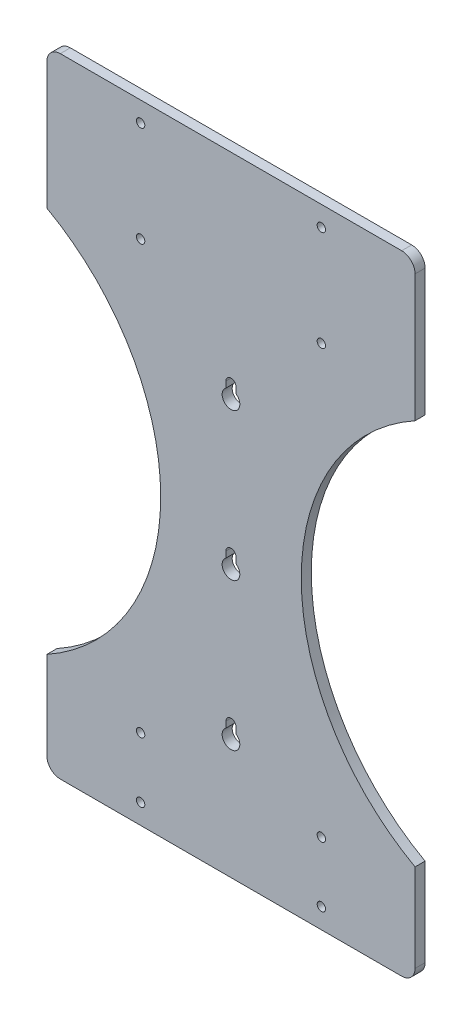
SolidWorks part; units mm, degrees
material "PC High Viscosity"
ref_plane "Front Plane" through (0, 0, 0) normal (0, 0, 1) x (1, 0, 0)
ref_plane "Top Plane" through (0, 0, 0) normal (0, 1, 0) x (1, 0, 0)
ref_plane "Right Plane" through (0, 0, 0) normal (1, 0, 0) x (0, 0, -1)
sketch "Sketch1" plane through (0, 0, 0) normal (0, 0, 1) x (1, 0, 0)
  line L0 (-174.625, 151.522) -> (-174.625, 311.15)
  line L1 (-174.625, -311.15) -> (174.625, -311.15)
  line L2 (-174.625, -311.15) -> (-174.625, -215.022)
  line L3 (-174.625, 311.15) -> (174.625, 311.15)
  line L4 (174.625, -311.15) -> (174.625, -215.022)
  line L5 (-174.625, -311.15) -> (174.625, 311.15) construction
  line L6 (-174.625, 311.15) -> (174.625, -311.15) construction
  line L7 (0, 311.15) -> (0, -311.15) construction
  line L8 (174.625, 151.522) -> (174.625, 311.15)
  arc A0 (-174.625, -215.022) -> (-174.625, 151.522) centre (-276.225, -31.75) ccw
  arc A1 (174.625, -215.022) -> (174.625, 151.522) centre (276.225, -31.75) cw
  point P0 (0, 0)
  dimension "D3" = 419.1
  dimension "D1" = 622.3
  dimension "D2" = 349.25
  dimension "D4" = 279.4
  dimension "D5" = 101.6
extrude "Boss-Extrude1" add sketch "Sketch1" along normal blind 9.525
sketch "Sketch2" plane through (0, 0, 9.525) normal (0, 0, 1) x (1, 0, 0)
  line L0 (0, 311.15) -> (0, -311.15) construction
  line L1 (174.625, 311.15) -> (-174.625, 311.15) construction
  line L2 (-174.625, -311.15) -> (174.625, -311.15) construction
  line L3 (-66.675, -31.75) -> (66.675, -31.75) construction
  arc A0 (-174.625, -215.022) -> (-174.625, 151.522) centre (-276.225, -31.75) ccw construction
  arc A1 (174.625, 151.522) -> (174.625, -215.022) centre (276.225, -31.75) ccw construction
  point P6 (0, -191.262)
  point P7 (0, 88.138)
  point P16 (0, -51.562)
  dimension "D2" = 119.888
  dimension "D1" = 279.4
  dimension "D3" = 139.7
hole_wizard "V (0.377) Diameter Slot1" positions "Sketch3" profile "Sketch5" size "V" standard "ANSI Inch" slot yes end condition through all
sketch "Sketch3" plane through (0, 0, 9.525) normal (0, 0, 1) x (1, 0, 0)
  line L0 (0, -202.3745) -> (0, -180.1495) construction
  point P0 (0, -191.262)
  point P3 (0, 88.138)
  point P8 (0, -51.562)
  dimension "D1" = 22.225
sketch "Sketch5" plane through (0, -191.262, 9.525) normal (1, 0, 0) x (0, -1, 0)
  line L0 (0, 0) -> (0, 9.525)
  line L1 (0, 9.525) -> (4.7879, 9.525)
  line L2 (4.7879, 9.525) -> (4.7879, 0)
  line L5 (4.7879, 0) -> (0, 0)
  line L11 (0, -6.35) -> (0, 107.95) construction
  dimension "Thru Hole Dia." = 9.5758
  dimension "Thru Hole Depth" = 9.525
sketch "Tetris" plane through (0, 0, 0) normal (0, 0, 1) x (1, 0, 0)
  line L0 (193.675, -215.022) -> (193.675, -311.15)
  line L1 (-174.625, 311.15) -> (1044.575, 311.15)
  line L2 (-174.625, 311.15) -> (-174.625, -2127.25)
  line L3 (-174.625, -2127.25) -> (1044.575, -2127.25)
  line L4 (1044.575, 311.15) -> (1044.575, -2127.25)
  line L5 (193.675, 311.15) -> (193.675, 151.522)
  line L6 (542.925, 311.15) -> (193.675, 311.15)
  line L7 (542.925, 151.522) -> (542.925, 311.15)
  line L8 (542.925, -311.15) -> (542.925, -215.022)
  line L9 (193.675, -311.15) -> (542.925, -311.15)
  line L10 (174.625, 151.522) -> (174.625, 311.15)
  line L11 (174.625, 311.15) -> (-174.625, 311.15)
  line L12 (-174.625, 311.15) -> (-174.625, 151.522)
  line L13 (-174.625, -215.022) -> (-174.625, -311.15)
  line L14 (-174.625, -311.15) -> (174.625, -311.15)
  line L15 (174.625, -311.15) -> (174.625, -215.022)
  line L16 (174.625, 151.522) -> (174.625, 311.15)
  line L17 (174.625, 311.15) -> (-174.625, 311.15)
  line L18 (-174.625, 311.15) -> (-174.625, 151.522)
  line L19 (-174.625, -215.022) -> (-174.625, -311.15)
  line L20 (-174.625, -311.15) -> (174.625, -311.15)
  line L21 (174.625, -311.15) -> (174.625, -215.022)
  line L22 (193.675, -862.722) -> (193.675, -958.85)
  line L23 (193.675, -336.55) -> (193.675, -496.178)
  line L24 (542.925, -336.55) -> (193.675, -336.55)
  line L25 (542.925, -496.178) -> (542.925, -336.55)
  line L26 (542.925, -958.85) -> (542.925, -862.722)
  line L27 (193.675, -958.85) -> (542.925, -958.85)
  line L28 (193.675, -1510.422) -> (193.675, -1606.55)
  line L29 (193.675, -984.25) -> (193.675, -1143.878)
  line L30 (542.925, -984.25) -> (193.675, -984.25)
  line L31 (542.925, -1143.878) -> (542.925, -984.25)
  line L32 (542.925, -1606.55) -> (542.925, -1510.422)
  line L33 (193.675, -1606.55) -> (542.925, -1606.55)
  line L34 (-174.625, -862.722) -> (-174.625, -958.85)
  line L35 (-174.625, -336.55) -> (-174.625, -496.178)
  line L36 (174.625, -336.55) -> (-174.625, -336.55)
  line L37 (174.625, -496.178) -> (174.625, -336.55)
  line L38 (174.625, -958.85) -> (174.625, -862.722)
  line L39 (-174.625, -958.85) -> (174.625, -958.85)
  line L40 (-174.625, -1510.422) -> (-174.625, -1606.55)
  line L41 (-174.625, -984.25) -> (-174.625, -1143.878)
  line L42 (174.625, -984.25) -> (-174.625, -984.25)
  line L43 (174.625, -1143.878) -> (174.625, -984.25)
  line L44 (174.625, -1606.55) -> (174.625, -1510.422)
  line L45 (-174.625, -1606.55) -> (174.625, -1606.55)
  line L46 (558.002, 311.15) -> (748.502, 311.15)
  line L47 (748.502, 311.15) -> (748.502, -311.15)
  line L48 (748.502, -311.15) -> (558.002, -311.15)
  line L49 (558.002, -311.15) -> (558.002, 311.15)
  line L51 (769.4566, -311.15) -> (959.9566, -311.15)
  line L52 (769.4566, -311.15) -> (769.4566, 311.15)
  line L53 (769.4566, 311.15) -> (959.9566, 311.15)
  line L54 (959.9566, -311.15) -> (959.9566, 311.15)
  line L55 (-174.625, -1698.7675) -> (447.675, -1698.7675)
  line L56 (-174.625, -1698.7675) -> (-174.625, -2048.0175)
  line L57 (-174.625, -2048.0175) -> (447.675, -2048.0175)
  line L58 (447.675, -1698.7675) -> (447.675, -2048.0175)
  arc A0 (193.675, -215.022) -> (193.675, 151.522) centre (92.075, -31.75) ccw
  arc A1 (542.925, 151.522) -> (542.925, -215.022) centre (644.525, -31.75) ccw
  arc A2 (-174.625, -215.022) -> (-174.625, 151.522) centre (-276.225, -31.75) ccw
  arc A3 (174.625, 151.522) -> (174.625, -215.022) centre (276.225, -31.75) ccw
  arc A4 (-174.625, -215.022) -> (-174.625, 151.522) centre (-276.225, -31.75) ccw
  arc A5 (174.625, 151.522) -> (174.625, -215.022) centre (276.225, -31.75) ccw
  arc A6 (193.675, -862.722) -> (193.675, -496.178) centre (92.075, -679.45) ccw
  arc A7 (542.925, -496.178) -> (542.925, -862.722) centre (644.525, -679.45) ccw
  arc A8 (193.675, -1510.422) -> (193.675, -1143.878) centre (92.075, -1327.15) ccw
  arc A9 (542.925, -1143.878) -> (542.925, -1510.422) centre (644.525, -1327.15) ccw
  arc A10 (-174.625, -862.722) -> (-174.625, -496.178) centre (-276.225, -679.45) ccw
  arc A11 (174.625, -496.178) -> (174.625, -862.722) centre (276.225, -679.45) ccw
  arc A12 (-174.625, -1510.422) -> (-174.625, -1143.878) centre (-276.225, -1327.15) ccw
  arc A13 (174.625, -1143.878) -> (174.625, -1510.422) centre (276.225, -1327.15) ccw
  dimension "D1" = 1219.2
  dimension "D2" = 2438.4
  dimension "D6" = 190.5
  dimension "D7" = 622.3
  dimension "D3" = 0
  dimension "D4" = 2
  dimension "D5" = 3
fillet "Fillet1" radius 12.7 2 edges at (174.625, -311.15, 4.7625) (-174.625, -311.15, 4.7625)
sketch "Sketch6" plane through (0, 0, 9.525) normal (0, 0, 1) x (1, 0, 0)
  circle A0 centre (0, -197.5866) radius 8.382
  circle A1 centre (0, 81.8134) radius 8.382
  circle A2 centre (0, -57.8866) radius 8.382
  dimension "D1" = 16.764
extrude "Cut-Extrude1" cut sketch "Sketch6" against normal through all
sketch "Sketch7" plane through (0, 0, 9.525) normal (0, 0, 1) x (1, 0, 0)
  line L0 (137.2235, 251.5345) -> (137.2235, 184.8595) construction
  line L6 (174.625, 311.15) -> (-174.625, 311.15) construction
  line L9 (174.625, 151.522) -> (174.625, 311.15) construction
  line L18 (0, 311.15) -> (0, -311.15) construction
  line L19 (-161.925, -311.15) -> (161.925, -311.15) construction
  line L20 (-137.2235, 251.5345) -> (-137.2235, 184.8595) construction
  point P4 (137.2235, 218.197)
  point P9 (-137.2235, 218.197)
  dimension "D1" = 66.675
  dimension "D2" = 37.4015
  dimension "D3" = 66.675
sketch "Sketch10" [suppressed] plane through (0, 0, 0) normal (0, 0, -1) x (-1, 0, 0)
  line L0 (174.625, 287.412) -> (142.875, 287.412)
  line L1 (137.16, 281.697) -> (137.16, 154.697)
  line L2 (137.16, 281.697) -> (137.16, 154.697) construction
  line L3 (174.625, 151.522) -> (142.875, 151.522) construction
  line L4 (139.7, 281.697) -> (139.7, 154.697) construction
  line L5 (174.625, 284.872) -> (142.875, 284.872) construction
  line L6 (0, 311.15) -> (0, -311.15) construction
  line L7 (-174.625, 311.15) -> (174.625, 311.15) construction
  line L8 (161.925, -311.15) -> (-161.925, -311.15) construction
  line L9 (-174.625, 151.522) -> (-174.625, 284.872) construction
  line L10 (-174.625, 284.872) -> (-142.875, 284.872) construction
  line L11 (-139.7, 281.697) -> (-139.7, 154.697) construction
  line L15 (174.625, 151.522) -> (174.625, 284.872) construction
  line L18 (-174.625, 151.522) -> (-142.875, 151.522) construction
  line L19 (174.625, 151.522) -> (140.335, 151.522)
  line L20 (174.625, 287.412) -> (174.625, 151.522)
  line L21 (-174.625, 151.522) -> (-174.625, 284.872) construction
  line L22 (-174.625, 284.872) -> (-142.875, 284.872) construction
  line L23 (-139.7, 281.697) -> (-139.7, 154.697) construction
  line L24 (-174.625, 151.522) -> (-142.875, 151.522) construction
  line L25 (-174.625, 287.412) -> (-174.625, 151.522)
  line L26 (-174.625, 151.522) -> (-140.335, 151.522)
  line L27 (-137.16, 281.697) -> (-137.16, 154.697)
  line L28 (-174.625, 287.412) -> (-142.875, 287.412)
  arc A0 (142.875, 287.412) -> (137.16, 281.697) centre (142.875, 281.697) ccw
  arc A1 (142.875, 284.872) -> (139.7, 281.697) centre (142.875, 281.697) ccw construction
  arc A2 (137.16, 154.697) -> (140.335, 151.522) centre (140.335, 154.697) ccw
  arc A3 (139.7, 154.697) -> (142.875, 151.522) centre (142.875, 154.697) ccw construction
  arc A4 (-139.7, 154.697) -> (-142.875, 151.522) centre (-142.875, 154.697) cw construction
  arc A5 (-142.875, 284.872) -> (-139.7, 281.697) centre (-142.875, 281.697) cw construction
  arc A6 (-139.7, 154.697) -> (-142.875, 151.522) centre (-142.875, 154.697) cw construction
  arc A7 (-142.875, 284.872) -> (-139.7, 281.697) centre (-142.875, 281.697) cw construction
  arc A8 (-137.16, 154.697) -> (-140.335, 151.522) centre (-140.335, 154.697) cw
  arc A9 (-142.875, 287.412) -> (-137.16, 281.697) centre (-142.875, 281.697) cw
  dimension "D3" = 3.175
  dimension "D5" = 3.175
  dimension "D1" = 133.35
  dimension "D2" = 34.925
  dimension "D4" = 2.54
extrude "Cut-Extrude2" [suppressed] cut sketch "Sketch10" against normal blind 3.175
sketch "Sketch11" plane through (0, 0, 0) normal (0, 0, -1) x (-1, 0, 0)
  line L0 (-85.725, 311.15) -> (-85.725, -311.15) construction
  line L1 (-174.625, 311.15) -> (174.625, 311.15) construction
  line L2 (-174.625, 151.522) -> (-174.625, 311.15) construction
  line L3 (0, 311.15) -> (0, -311.15) construction
  line L4 (85.725, 311.15) -> (85.725, 55.5481) construction
  line L5 (161.925, -311.15) -> (-161.925, -311.15) construction
  line L6 (85.725, 311.15) -> (85.725, -311.15) construction
  point P1 (-85.725, -234.95)
  point P6 (-85.725, -292.1)
  point P10 (-85.725, 265.938)
  point P11 (-85.725, 170.688)
  point P18 (85.725, 170.688)
  point P19 (85.725, 265.938)
  point P23 (85.725, -292.1)
  point P24 (85.725, -234.95)
  dimension "D1" = 88.9
  dimension "D2" = 95.25
  dimension "D3" = 45.212
  dimension "D4" = 19.05
  dimension "D5" = 57.15
hole_wizard "5/16 (0.3125) Diameter Hole1" positions "Sketch12" profile "Sketch13" hole size "5/16" standard "ANSI Inch" end condition through all
sketch "Sketch12" plane through (0, 0, 0) normal (0, 0, -1) x (-1, 0, 0)
  point P18 (-85.725, 265.938)
  point P25 (85.725, 170.688)
  point P28 (85.725, 265.938)
  point P33 (-85.725, 170.688)
  point P36 (85.725, -234.95)
  point P39 (85.725, -292.1)
  point P42 (-85.725, -292.1)
  point P45 (-85.725, -234.95)
sketch "Sketch13" plane through (85.725, 265.938, 0) normal (1, 0, 0) x (0, 1, 0)
  line L0 (0, 0) -> (0, 9.525)
  line L1 (0, 9.525) -> (3.9687, 9.525)
  line L2 (3.9687, 9.525) -> (3.9687, 0)
  line L5 (3.9687, 0) -> (0, 0)
  line L11 (0, -6.35) -> (0, 107.95) construction
  dimension "Thru Hole Dia." = 7.9375
  dimension "Thru Hole Depth" = 9.525
sketch "Sketch14" plane through (0, 0, 0) normal (0, 0, -1) x (-1, 0, 0)
  line L0 (174.625, 311.15) -> (174.625, 151.522) construction
  line L1 (-174.625, 311.15) -> (174.625, 311.15)
  line L2 (-174.625, 311.15) -> (-174.625, 284.872)
  line L3 (-174.625, 284.872) -> (174.625, 284.872)
  line L4 (174.625, 311.15) -> (174.625, 284.872)
  dimension "D1" = 133.35
extrude "Cut-Extrude3" cut sketch "Sketch14" against normal through all
fillet "Fillet2" radius 12.7 2 edges at (-174.625, 284.872, 4.7625) (174.625, 284.872, 4.7625)
equation "\"D2@Sketch7\"=1.3875+.17/2"
equation "\"D5@Sketch10\"=\"D3@Sketch10\""
equation "\"D3@Sketch2\"=\"D1@Sketch2\"/2"
